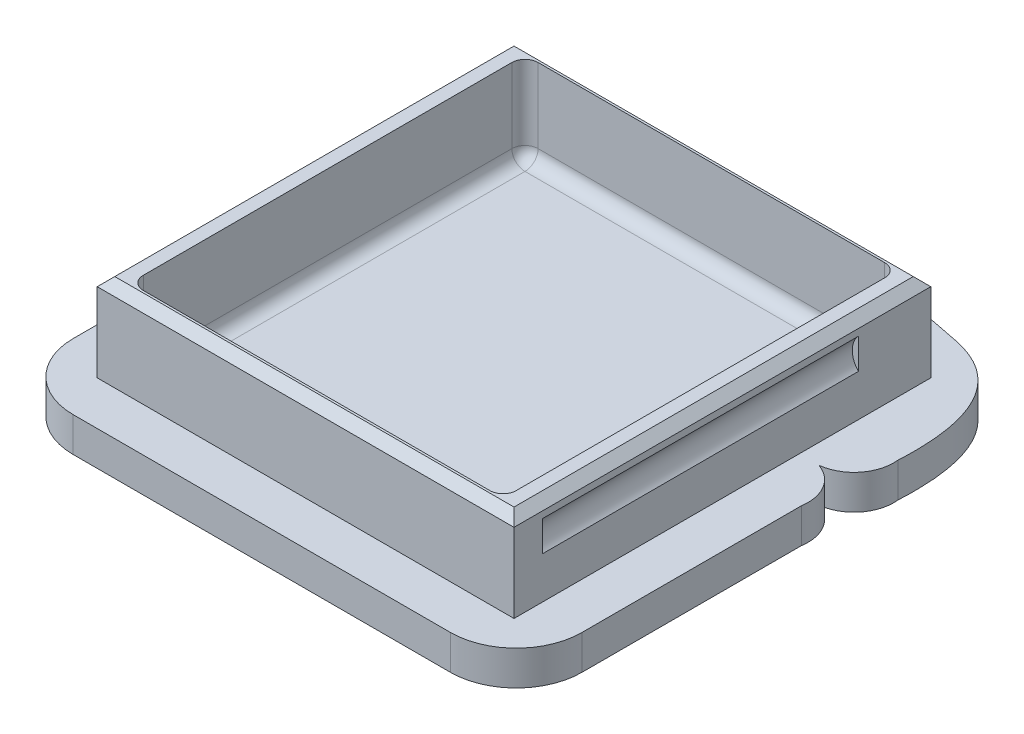
SolidWorks part; units mm, degrees
material "Oak"
ref_plane "Front Plane" through (0, 0, 0) normal (0, 0, 1) x (1, 0, 0)
ref_plane "Top Plane" through (0, 0, 0) normal (0, 1, 0) x (1, 0, 0)
ref_plane "Right Plane" through (0, 0, 0) normal (1, 0, 0) x (0, 0, -1)
sketch "Sketch2" plane through (0, 0, 0) normal (0, 1, 0) x (1, 0, 0)
  line L0 (-66.04, 22.225) -> (66.04, 22.225)
  line L1 (63.5, -66.675) -> (-63.5, -66.675)
  line L2 (63.5, -66.675) -> (63.5, 66.675)
  line L3 (63.5, 66.675) -> (-63.5, 66.675)
  line L4 (-63.5, -66.675) -> (-63.5, 66.675)
  line L5 (63.5, -66.675) -> (-63.5, 66.675) construction
  line L6 (63.5, 66.675) -> (-63.5, -66.675) construction
  line L7 (-73.66, 9.525) -> (-73.66, -53.975)
  line L8 (-54.61, -73.025) -> (54.61, -73.025)
  line L9 (73.66, -53.975) -> (73.66, 9.525)
  line L10 (-73.66, 9.525) -> (-73.66, 13.1711)
  arc A0 (-73.66, 9.525) -> (-66.04, 22.225) centre (-62.3051, 11.348) cw
  arc A1 (73.66, 9.525) -> (66.04, 22.225) centre (62.3051, 11.348) ccw
  arc A2 (-66.04, 22.225) -> (-76.2, 34.925) centre (-64.77, 33.655) cw
  arc A3 (66.04, 22.225) -> (76.2, 34.925) centre (64.77, 33.655) ccw
  arc A4 (-54.2615, 73.3341) -> (54.2615, 73.3341) centre (0, -178.2209) cw
  arc A5 (73.66, -53.975) -> (54.61, -73.025) centre (54.61, -53.975) cw
  arc A6 (-73.66, -53.975) -> (-54.61, -73.025) centre (-54.61, -53.975) ccw
  spline S0 degree 2 poles (-54.2615, 73.3341) (-78.0337, 68.7721) (-76.2, 34.925) knots 0 0 0 1 1 1
  spline S1 degree 2 poles (54.2615, 73.3341) (78.0337, 68.7721) (76.2, 34.925) knots 0 0 0 1 1 1
  point P0 (0, 0)
  dimension "D11" = 11.5003
  dimension "D12" = 11.5003
  dimension "D14" = 11.5003
  dimension "D15" = 11.5003
  dimension "D17" = 19.05
  dimension "D1" = 133.35
  dimension "D2" = 127
  dimension "D3" = 44.45
  dimension "D4" = 2.54
  dimension "D5" = 2.54
  dimension "D6" = 10.16
  dimension "D7" = 10.16
  dimension "D8" = 6.35
  dimension "D9" = 12.7
  dimension "D10" = 12.7
  dimension "D13" = 12.7
extrude "Boss-Extrude1" add sketch "Sketch2" along normal blind 10 contours L7 A6 L8 A5 L9 A1 L0 L2 L1 L4 A0 L10 | L4 L1 L2 L0 | L4 L0 L2 | A2 L0 L4 L10 | S1 A4 S0 L10 L4 L3 L2 | L4 L2 L3 | L0 A3 L2 region at (-72.4781, 0, -27.4885) region at (-64.77, 0, -20.4695) region at (0, 0, -44.45) region at (0, 0, 22.225)
sketch "Sketch3" plane through (0, 10, 0) normal (0, 1, 0) x (1, 0, 0)
  line L1 (-53.975, 57.15) -> (53.975, 57.15)
  line L2 (-53.975, 57.15) -> (-53.975, -57.15)
  line L3 (-53.975, -57.15) -> (53.975, -57.15)
  line L4 (53.975, 57.15) -> (53.975, -57.15)
  line L5 (-53.975, 57.15) -> (53.975, -57.15) construction
  line L6 (-53.975, -57.15) -> (53.975, 57.15) construction
  line L8 (-60.325, 60.325) -> (60.325, 60.325)
  line L9 (-60.325, 60.325) -> (-60.325, -60.325)
  line L10 (-60.325, -60.325) -> (60.325, -60.325)
  line L11 (60.325, 60.325) -> (60.325, -60.325)
  line L12 (-60.325, 60.325) -> (60.325, -60.325) construction
  line L13 (-60.325, -60.325) -> (60.325, 60.325) construction
  point P0 (0, 0)
  point P10 (0, 0)
  dimension "D1" = 107.95
  dimension "D2" = 114.3
  dimension "D3" = 6.35
  dimension "D4" = 3.175
extrude "Boss-Extrude2" add sketch "Sketch3" along normal blind 25.4
fillet "Fillet2" radius 3.81 4 edges at (53.975, 10, 0) (0, 10, -57.15) (-53.975, 10, 0) (0, 10, 57.15)
sketch "Sketch5" plane through (0, 0, 0) normal (0, 0, 1) x (1, 0, 0)
  line L2 (60.325, 30.9167) -> (60.325, 22.1033)
  line L4 (-60.325, 30.9167) -> (-60.325, 22.1033)
  arc A0 (60.325, 30.9167) -> (60.325, 22.1033) centre (64.897, 26.51) ccw
  arc A1 (-60.325, 30.9167) -> (-60.325, 22.1033) centre (-64.897, 26.51) cw
  dimension "D2" = 12.7
extrude "Cut-Extrude2" cut sketch "Sketch5" against normal blind 39.37 and the other way blind 52.07
fillet "Fillet3" radius 3.81 8 edges at (52.8591, 11.1159, 56.0341) (52.8591, 11.1159, -56.0341) (-52.8591, 11.1159, -56.0341) (-52.8591, 11.1159, 56.0341) (53.975, 24.605, 57.15) (53.975, 24.605, -57.15) (-53.975, 24.605, -57.15) (-53.975, 24.605, 57.15)
chamfer "Chamfer1" distance 2.54 angle 45 4 edges at (0, 35.4, 60.325) (-60.325, 35.4, 0) (0, 35.4, -60.325) (60.325, 35.4, 0)
